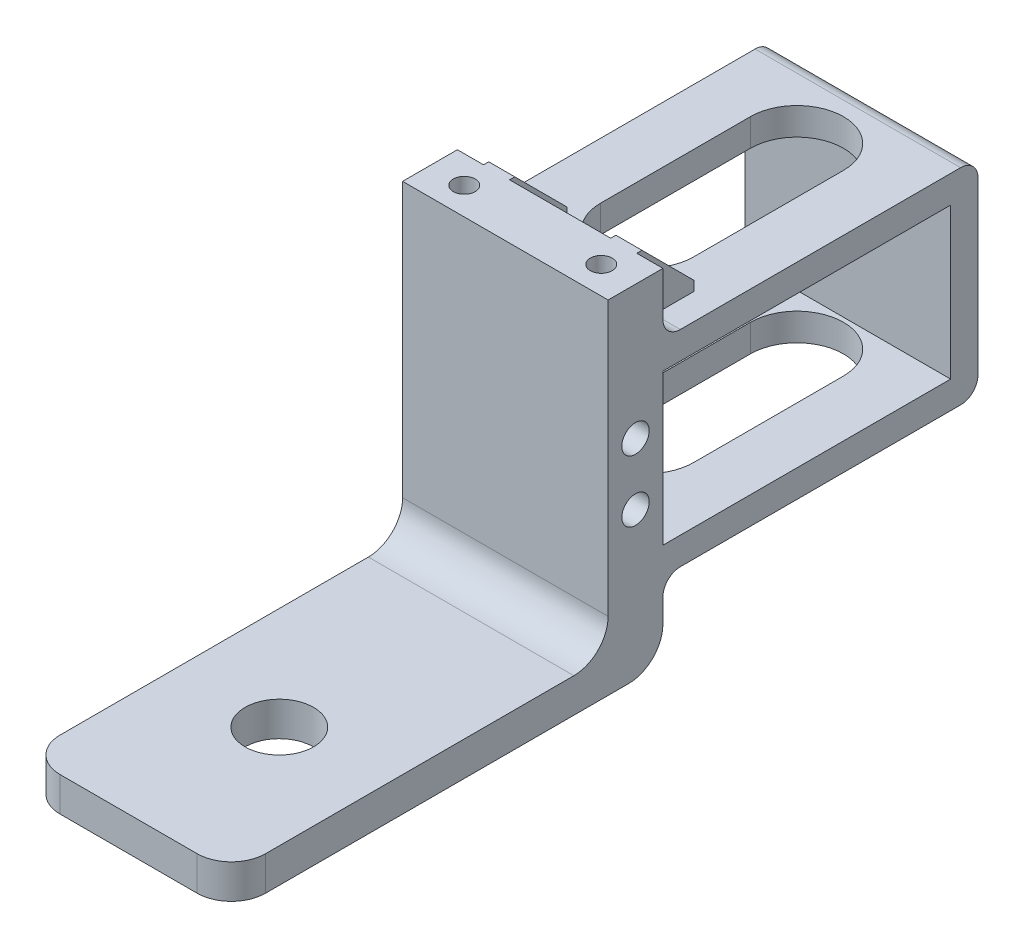
SolidWorks part; units mm, degrees
ref_plane "Front Plane" through (0, 0, 0) normal (0, 0, 1) x (1, 0, 0)
ref_plane "Top Plane" through (0, 0, 0) normal (0, 1, 0) x (1, 0, 0)
ref_plane "Right Plane" through (0, 0, 0) normal (1, 0, 0) x (0, 0, -1)
sketch "Sketch1" plane through (0, 0, 0) normal (1, 0, 0) x (0, 0, -1)
  line L1 (0, 0) -> (63, 0)
  line L2 (0, 0) -> (0, 5)
  line L3 (0, 5) -> (63, 5)
  line L4 (63, 0) -> (63, 5)
  dimension "D1" = 5
  dimension "D2" = 63
extrude "Boss-Extrude1" add sketch "Sketch1" along normal blind 30 contours L3 L4 L1 L2
sketch "Sketch2" plane through (0, 5, 0) normal (0, 1, 0) x (1, 0, 0)
  line L0 (30, 0) -> (30, 63) construction
  line L1 (0, 63) -> (30, 63)
  line L2 (0, 63) -> (0, 55)
  line L3 (0, 55) -> (30, 55)
  line L4 (30, 63) -> (30, 55)
  dimension "D1" = 8
extrude "Boss-Extrude2" add sketch "Sketch2" along normal blind 45
sketch "Sketch3" plane through (0, 5, 0) normal (0, 1, 0) x (1, 0, 0)
  line L0 (30, 0) -> (0, 0) construction
  circle A0 centre (15, 22) radius 5
  point P4 (15, 0)
  dimension "D2" = 10
  dimension "D1" = 22
extrude "Cut-Extrude1" cut sketch "Sketch3" against normal through all
sketch "Sketch5" plane through (0, 50, 0) normal (0, 1, 0) x (1, 0, 0)
  line L0 (0, 63) -> (0, 55) construction
  line L1 (30, 55) -> (30, 63) construction
  circle A0 centre (5, 59) radius 1.6
  circle A1 centre (25, 59) radius 1.6
  point P5 (0, 59)
  dimension "D1" = 3.2
  dimension "D3" = 5
  dimension "D2" = 5
extrude "Cut-Extrude3" cut sketch "Sketch5" against normal blind 14
fillet "Fillet1" radius 5 4 edges at (15, 0, -63) (15, 5, -55) (30, 2.5, 0) (0, 2.5, 0)
sketch "Sketch6" plane through (30, 0, 0) normal (1, 0, 0) x (0, 0, -1)
  line L0 (63, 5) -> (63, 50) construction
  line L1 (63, 37) -> (105, 37)
  line L2 (63, 37) -> (63, 15)
  line L3 (63, 15) -> (105, 15)
  line L4 (105, 37) -> (105, 15)
  line L5 (5, 0) -> (58, 0) construction
  line L6 (63, 41) -> (109, 41)
  line L7 (63, 41) -> (63, 11)
  line L8 (63, 11) -> (109, 11)
  line L9 (109, 41) -> (109, 11)
  line M11 (63, 5) -> (63, 50)
  dimension "D1" = 4
  dimension "D2" = 4
  dimension "D3" = 4
  dimension "D4" = 22
  dimension "D5" = 42
  dimension "D6" = 15
extrude "Boss-Extrude3" add sketch "Sketch6" against normal up to surface (30 mm away) contours L9 L6 L1 L4 L3 L8 M11 region at (30, 39, -63.5492) up to face at (0, 15.3661, -44.5089)
sketch "Sketch7" plane through (30, 0, 0) normal (1, 0, 0) x (0, 0, -1)
  line L0 (63, 15) -> (63, 37) construction
  line L1 (59, 30.5) -> (59, 21.5)
  circle A0 centre (59, 30.5) radius 2
  circle A1 centre (59, 21.5) radius 2
  point P4 (59, 26)
  point P8 (63, 26)
  dimension "D1" = 4
  dimension "D2" = 9
  dimension "D3" = 4
extrude "Cut-Extrude4" cut sketch "Sketch7" against normal blind 7.62 contours A0 | A1 region at (30, 22.8742, -60.3742) region at (30, 31.8742, -57.6258)
fillet "Fillet2" radius 2.54 4 edges at (15, 11, -109) (15, 11, -63) (15, 41, -63) (15, 41, -109)
sketch "Sketch8" plane through (0, 41, 0) normal (0, 1, 0) x (1, 0, 0)
  line L0 (15, 97.57) -> (15, 75.7) construction
  line L1 (21.7934, 97.57) -> (21.7934, 75.7)
  line L2 (8.2066, 97.57) -> (8.2066, 75.7)
  line L3 (0, 65.54) -> (30, 65.54) construction
  line L4 (30, 106.46) -> (0, 106.46) construction
  arc A0 (21.7934, 97.57) -> (8.2066, 97.57) centre (15, 97.57) ccw
  arc A1 (8.2066, 75.7) -> (21.7934, 75.7) centre (15, 75.7) ccw
  point P2 (15, 86.635)
  point P7 (15, 65.54)
  point P8 (15, 75.4616)
  dimension "D1" = 8.89
  dimension "D2" = 10.16
extrude "Cut-Extrude5" cut sketch "Sketch8" against normal through all
sketch "Sketch9" plane through (0, 41, 0) normal (0, 1, 0) x (1, 0, 0)
  line L0 (30, 63) -> (0, 63) construction
  line L1 (3.81, 63) -> (7.62, 63)
  line L2 (3.81, 63) -> (3.81, 71.3781)
  line L3 (3.81, 71.3781) -> (7.62, 71.3781)
  line L4 (7.62, 63) -> (7.62, 71.3781)
  line L5 (0, 65.54) -> (0, 106.46) construction
  line L6 (22.38, 63) -> (26.19, 63)
  line L7 (22.38, 63) -> (22.38, 71.3781)
  line L8 (22.38, 71.3781) -> (26.19, 71.3781)
  line L9 (26.19, 63) -> (26.19, 71.3781)
  line L10 (30, 65.54) -> (30, 106.46) construction
  dimension "D1" = 3.81
  dimension "D2" = 3.81
  dimension "D3" = 3.81
extrude "Boss-Extrude4" add sketch "Sketch9" along normal up to surface (9 mm away) up to face at (5, 50, -57.4)
chamfer "Chamfer1" distance 7.62 angle 45 2 edges at (5.715, 50, -71.3781) (24.285, 50, -71.3781)
sketch "Sketch10" plane through (0, 11, 0) normal (0, -1, 0) x (1, 0, 0)
  line L1 (3.81, -63) -> (7.62, -63)
  line L2 (3.81, -63) -> (3.81, -71.3781)
  line L3 (3.81, -71.3781) -> (7.62, -71.3781)
  line L4 (7.62, -63) -> (7.62, -71.3781)
  line L5 (22.38, -63) -> (26.19, -63)
  line L6 (22.38, -63) -> (22.38, -71.3781)
  line L7 (22.38, -71.3781) -> (26.19, -71.3781)
  line L8 (26.19, -63) -> (26.19, -71.3781)
extrude "Boss-Extrude5" add sketch "Sketch10" along normal up to vertex (6 mm away) up to point (30, 5, -63)
chamfer "Chamfer2" distance 7.62 angle 45 2 edges at (24.285, 5, -71.3781) (5.715, 5, -71.3781)
ref_plane "Plane2" through (15, 0, 0) normal (1, 0, 0) x (0, 0, -1)
mirror "Mirror3" about plane through (15, 0, 0) normal (1, 0, 0) of "Cut-Extrude4"
